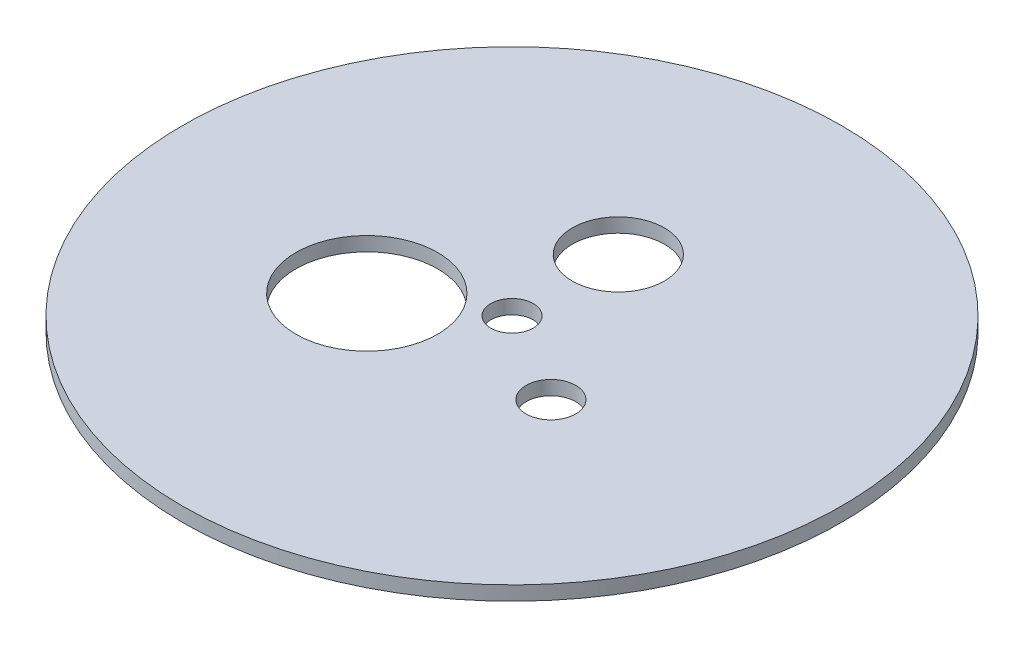
SolidWorks part; units mm, degrees
ref_plane "Front Plane" through (0, 0, 0) normal (0, 0, 1) x (1, 0, 0)
ref_plane "Top Plane" through (0, 0, 0) normal (0, 1, 0) x (1, 0, 0)
ref_plane "Right Plane" through (0, 0, 0) normal (1, 0, 0) x (0, 0, -1)
sketch "Sketch1" plane through (0, 0, 0) normal (0, 1, 0) x (1, 0, 0)
  line L0 (0, 15) -> (0, 0) construction
  line L1 (0, 0) -> (-12.9904, -7.5) construction
  line L2 (0, 0) -> (12.9904, -7.5) construction
  circle A0 centre (0, 0) radius 46.5
  circle A1 centre (0, 15) radius 6.5
  circle A2 centre (-12.9904, -7.5) radius 10
  circle A3 centre (12.9904, -7.5) radius 3.5
  circle A4 centre (0, 0) radius 3
  point P3 (0, 15)
  point P8 (12.9904, -7.5)
  point P9 (-12.9904, -7.5)
  point P10 (0, 0)
  dimension "D1" = 93
  dimension "D4" = 13
  dimension "D5" = 20
  dimension "D6" = 6
  dimension "D7" = 7
  dimension "D2" = 15
  dimension "D3" = 3
extrude "Boss-Extrude1" add sketch "Sketch1" along normal blind 2
sketch "Sketch2" plane through (0, 2, 0) normal (0, 1, 0) x (1, 0, 0)
  line L0 (0, 0) -> (12.9904, -7.5) construction
  line L1 (0, 0) -> (0, 46.5) construction
  line L2 (0, 0) -> (-12.9904, -7.5) construction
  line L3 (0, 0) -> (-40.2702, -23.25) construction
  line L4 (0, 0) -> (40.2702, -23.25) construction
  circle A0 centre (0, 0) radius 46.5 construction
  circle A1 centre (-12.9904, -7.5) radius 10 construction
  circle A2 centre (12.9904, -7.5) radius 3.5 construction
  circle A3 centre (0, 0) radius 25
  circle A4 centre (21.6506, -12.5) radius 3
  circle A5 centre (-21.6506, -12.5) radius 3
  circle A6 centre (0, 25) radius 3
  point P22 (0, 0)
  dimension "D1" = 50
  dimension "D2" = 6
  dimension "D3" = 3
